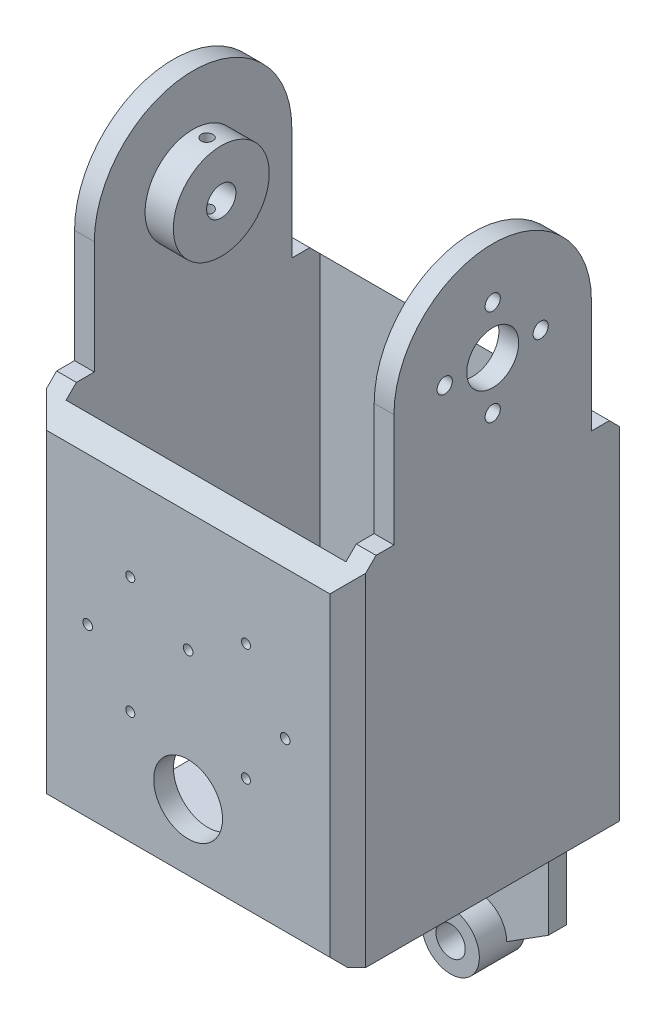
SolidWorks part; units mm, degrees
material "PLA"
ref_plane "Front Plane" through (0, 0, 0) normal (0, 0, 1) x (1, 0, 0)
ref_plane "Top Plane" through (0, 0, 0) normal (0, 1, 0) x (1, 0, 0)
ref_plane "Right Plane" through (0, 0, 0) normal (1, 0, 0) x (0, 0, -1)
sketch "Sketch1" plane through (0, 0, 0) normal (1, 0, 0) x (0, 0, -1)
  line L0 (-17.5, 0) -> (-17.5, -20)
  line L1 (17.5, 0) -> (17.5, -20)
  line L2 (17.5, -20) -> (22.5, -20)
  line L3 (-17.5, -20) -> (-22.5, -20)
  line L4 (22.5, -20) -> (22.5, -76)
  line L5 (-22.5, -20) -> (-22.5, -76)
  line L6 (22.5, -76) -> (-22.5, -76)
  arc A0 (17.5, 0) -> (-17.5, 0) centre (0, 0) ccw
  circle A1 centre (0, 0) radius 4.6
  dimension "D1" = 35
  dimension "D7" = 9.2
  dimension "D2" = 20
  dimension "D3" = 5
  dimension "D4" = 5
  dimension "D5" = 56
  dimension "D6" = 56
extrude "Boss-Extrude1" add sketch "Sketch1" against normal blind 3.5
sketch "Sketch2" plane through (0, 0, 0) normal (1, 0, 0) x (0, 0, -1)
  line L7 (-17.5, 0) -> (-17.5, -20)
  line L8 (-17.5, -20) -> (-22.5, -20)
  line L9 (-22.5, -20) -> (-22.5, -76)
  line L10 (-22.5, -76) -> (22.5, -76)
  line L11 (22.5, -76) -> (22.5, -20)
  line L12 (22.5, -20) -> (17.5, -20)
  line L13 (17.5, -20) -> (17.5, 0)
  line L16 (-22.5, -20) -> (-22.5, -76)
  line L17 (-22.5, -76) -> (22.5, -76)
  line L18 (22.5, -76) -> (22.5, -20)
  line L28 (-22.5, -20) -> (-25.675, -20)
  line L29 (-25.675, -20) -> (-25.675, -79.175)
  line L30 (22.5, -20) -> (25.675, -20)
  line L31 (25.675, -20) -> (25.675, -79.175)
  line L45 (-25.675, -79.175) -> (25.675, -79.175)
  arc A1 (17.5, 0) -> (-17.5, 0) centre (0, 0) ccw
  dimension "D2" = 3.175
  dimension "D3" = 3.175
  dimension "D1" = 0
extrude "Boss-Extrude2" add sketch "Sketch2" along normal blind 49.6 and the other way blind 3.5
chamfer "Chamfer2" distance 5 angle 45 2 edges at (23.05, -20, -25.675) (23.05, -20, 25.675)
sketch "Sketch4" plane through (0, -76, 0) normal (0, 1, 0) x (1, 0, 0)
  line L1 (0, 22.5) -> (49.6, 22.5)
  line L2 (0, 22.5) -> (0, -22.5)
  line L3 (0, -22.5) -> (49.6, -22.5)
  line L4 (49.6, 22.5) -> (49.6, -22.5)
extrude "Cut-Extrude1" cut sketch "Sketch4" against normal up to next
sketch "Sketch5" plane through (49.6, 0, 0) normal (1, 0, 0) x (0, 0, -1)
  line L9 (20.675, -20) -> (17.5, -20)
  line L10 (25.675, -25) -> (20.675, -20)
  line L11 (25.675, -79.175) -> (25.675, -25)
  line L12 (-25.675, -79.175) -> (25.675, -79.175)
  line L13 (-25.675, -25) -> (-25.675, -79.175)
  line L14 (-20.675, -20) -> (-25.675, -25)
  line L15 (-17.5, -20) -> (-20.675, -20)
  line L16 (-17.5, 0) -> (-17.5, -20)
  line L17 (17.5, -20) -> (17.5, 0)
  line L18 (20.675, -20) -> (17.5, -20)
  line L19 (25.675, -25) -> (20.675, -20)
  line L20 (25.675, -79.175) -> (25.675, -25)
  line L21 (-25.675, -79.175) -> (25.675, -79.175)
  line L22 (-25.675, -25) -> (-25.675, -79.175)
  line L23 (-20.675, -20) -> (-25.675, -25)
  line L24 (-17.5, -20) -> (-20.675, -20)
  line L25 (-17.5, 0) -> (-17.5, -20)
  line L26 (17.5, -20) -> (17.5, 0)
  circle A0 centre (0, 0) radius 4.6 construction
  arc A1 (17.5, 0) -> (-17.5, 0) centre (0, 0) ccw
  arc A2 (17.5, 0) -> (-17.5, 0) centre (0, 0) ccw
  circle A3 centre (0, 0) radius 4.6
  dimension "D1" = 0
extrude "Boss-Extrude3" add sketch "Sketch5" along normal blind 3.5
chamfer "Chamfer3" distance 3.175 angle 45 4 edges at (53.1, -52.0875, -25.675) (-3.5, -52.0875, -25.675) (53.1, -52.0875, 25.675) (-3.5, -52.0875, 25.675)
sketch "Sketch6" plane through (0, 0, 0) normal (1, 0, 0) x (0, 0, -1)
  circle A0 centre (0, 0) radius 8.5
  circle A1 centre (0, 0) radius 2.6
  dimension "D1" = 17
  dimension "D2" = 5.2
extrude "Boss-Extrude4" add sketch "Sketch6" along normal blind 5
sketch "Sketch7" plane through (0, -79.175, 0) normal (0, -1, 0) x (1, 0, 0)
  line L0 (2.5, 8.5) -> (2.5, -8.5) construction
  line L1 (5, 8.5) -> (0, 8.5) construction
  line L2 (0, -8.5) -> (5, -8.5) construction
  line L3 (5, 0) -> (0, 0) construction
  line L4 (5, -8.5) -> (5, 8.5) construction
  circle A0 centre (2.5, 0) radius 1.025
  dimension "D1" = 2.05
extrude "Cut-Extrude2" cut sketch "Sketch7" against normal through all
sketch "Sketch9" plane through (53.1, 0, 0) normal (1, 0, 0) x (0, 0, -1)
  circle A0 centre (0, 0) radius 8.5 construction
  circle A1 centre (0, 8.5) radius 1.35
  circle A2 centre (8.5, 0) radius 1.35
  circle A3 centre (0, -8.5) radius 1.35
  circle A4 centre (-8.5, 0) radius 1.35
  dimension "D1" = 17
  dimension "D2" = 2.7
  dimension "D3" = 2.7
  dimension "D4" = 2.7
  dimension "D5" = 2.7
extrude "Cut-Extrude3" cut sketch "Sketch9" against normal up to next
sketch "Sketch10" plane through (0, -79.175, 0) normal (0, -1, 0) x (1, 0, 0)
  line L0 (8.8, 25.675) -> (40.8, 25.675)
  line L1 (-0.325, 25.675) -> (49.925, 25.675) construction
  line L3 (8.8, 25.675) -> (40.8, 25.675)
  line L4 (8.8, 25.675) -> (8.8, -14.325)
  line L5 (8.8, -14.325) -> (40.8, -14.325)
  line L6 (40.8, 25.675) -> (40.8, -14.325)
  line L7 (0, -22.5) -> (0, 22.5) construction
  line L8 (49.6, 22.5) -> (49.6, -22.5) construction
  point P5 (24.8, 25.675)
  line M7 (49.925, 25.675) -> (-0.325, 25.675)
  line M13 (0, 22.5) -> (49.6, 22.5)
  dimension "D1" = 8.8
  dimension "D2" = 40
  dimension "D3" = 8.8
extrude "Boss-Extrude5" add sketch "Sketch10" along normal blind 3.175 contours L6 L4 L5 M13 | L6 L4 M7 M13
chamfer "Chamfer4" distance 1.5785 angle 45 1 edges at (24.8, -82.35, 25.675)
sketch "Sketch11" plane through (0, -79.175, 0) normal (0, -1, 0) x (1, 0, 0)
  line L16 (49.925, 25.675) -> (40.8, 25.675)
  line L17 (40.8, 25.675) -> (40.8, 22.5)
  line L18 (40.8, 22.5) -> (49.6, 22.5)
  line L19 (49.6, 22.5) -> (49.6, -22.5)
  line L20 (49.6, -22.5) -> (0, -22.5)
  line L21 (0, -22.5) -> (0, 22.5)
  line L22 (0, 22.5) -> (8.8, 22.5)
  line L23 (8.8, 22.5) -> (8.8, 25.675)
  line L24 (8.8, 25.675) -> (-0.325, 25.675)
  line L25 (-0.325, 25.675) -> (-3.5, 22.5)
  line L26 (-3.5, 22.5) -> (-3.5, -22.5)
  line L27 (-3.5, -22.5) -> (-0.325, -25.675)
  line L28 (-0.325, -25.675) -> (49.925, -25.675)
  line L29 (49.925, -25.675) -> (53.1, -22.5)
  line L30 (53.1, -22.5) -> (53.1, 22.5)
  line L31 (53.1, 22.5) -> (49.925, 25.675)
  line L32 (49.925, 25.675) -> (40.8, 25.675)
  line L33 (40.8, 25.675) -> (40.8, 22.5)
  line L34 (40.8, 22.5) -> (49.6, 22.5)
  line L35 (49.6, 22.5) -> (49.6, -22.5)
  line L36 (49.6, -22.5) -> (0, -22.5)
  line L37 (0, -22.5) -> (0, 22.5)
  line L38 (0, 22.5) -> (8.8, 22.5)
  line L39 (8.8, 22.5) -> (8.8, 25.675)
  line L40 (8.8, 25.675) -> (-0.325, 25.675)
  line L41 (-0.325, 25.675) -> (-3.5, 22.5)
  line L42 (-3.5, 22.5) -> (-3.5, -22.5)
  line L43 (-3.5, -22.5) -> (-0.325, -25.675)
  line L44 (-0.325, -25.675) -> (49.925, -25.675)
  line L45 (49.925, -25.675) -> (53.1, -22.5)
  line L46 (53.1, -22.5) -> (53.1, 22.5)
  line L47 (53.1, 22.5) -> (49.925, 25.675)
  dimension "D1" = 0
extrude "Boss-Extrude6" add sketch "Sketch11" along normal blind 3.175
chamfer "Chamfer5" distance 1.5785 angle 45 2 edges at (4.2375, -82.35, 25.675) (45.3625, -82.35, 25.675)
sketch "Sketch12" plane through (0, 0, 25.675) normal (0, 0, 1) x (1, 0, 0)
  line L0 (14.55, -39.265) -> (14.55, -40.865) construction
  line L1 (35.05, -39.265) -> (35.05, -40.865) construction
  line L2 (35.05, -59.965) -> (35.05, -61.565) construction
  circle A0 centre (24.8, -69.065) radius 6.1
  circle A1 centre (14.55, -40.065) radius 0.8
  circle A2 centre (35.05, -40.065) radius 0.8
  circle A3 centre (35.05, -60.765) radius 0.8
  circle A4 centre (14.55, -60.765) radius 0.8
  dimension "D1" = 12.2
extrude "Cut-Extrude4" cut sketch "Sketch12" against normal up to next
sketch "Sketch13" plane through (0, 0, 22.5) normal (0, 0, -1) x (-1, 0, 0)
  line L0 (-12.4437, -36.1489) -> (-12.4437, -39.9149) construction
  line L1 (-12.4437, -38.0319) -> (-16.9437, -38.0319)
  line L2 (-12.4437, -38.0319) -> (-12.4437, -63.7774)
  line L3 (-12.4437, -63.7774) -> (-16.9437, -63.7774)
  line L4 (-16.9437, -38.0319) -> (-16.9437, -63.7774)
  line L6 (-37.1796, -63.7774) -> (-32.6796, -63.7774)
  line L7 (-37.1796, -63.7774) -> (-37.1796, -38.0319)
  line L8 (-37.1796, -38.0319) -> (-32.6796, -38.0319)
  line L9 (-32.6796, -63.7774) -> (-32.6796, -38.0319)
  circle A0 centre (-35.05, -40.065) radius 0.8 construction
  circle A1 centre (-35.05, -60.765) radius 0.8 construction
  circle A2 centre (-14.55, -60.765) radius 0.8 construction
  circle A3 centre (-14.55, -40.065) radius 0.8 construction
  circle A4 centre (-35.05, -40.065) radius 0.8
  circle A5 centre (-35.05, -60.765) radius 0.8
  circle A6 centre (-14.55, -60.765) radius 0.8
  circle A7 centre (-14.55, -40.065) radius 0.8
  dimension "D1" = 4.5
  dimension "D2" = 4.5
extrude "Boss-Extrude7" add sketch "Sketch13" along normal blind 2.9
sketch "Sketch14" plane through (0, 0, 22.5) normal (0, 0, -1) x (-1, 0, 0)
  line L0 (-35.05, -60.765) -> (-14.55, -60.765) construction
  line L1 (-32.6796, -63.7774) -> (-32.6796, -38.0319) construction
  line L2 (-32.6796, -60.765) -> (-16.9472, -60.765)
  line L3 (-32.6796, -60.765) -> (-32.6796, -79.175)
  line L4 (-32.6796, -79.175) -> (-16.9472, -79.175)
  line L5 (-16.9472, -60.765) -> (-16.9472, -79.175)
  line L6 (-8.8, -79.175) -> (-40.8, -79.175) construction
  circle A0 centre (-24.8, -69.065) radius 6.1 construction
  circle A1 centre (-24.8, -69.065) radius 6.1
extrude "Boss-Extrude8" add sketch "Sketch14" along normal blind 0.325
sketch "Sketch20" plane through (0, 0, -25.675) normal (0, 0, -1) x (-1, 0, 0)
  line L0 (3.5, -82.35) -> (-53.1, -82.35) construction
  line L1 (-37.3, -79.38) -> (-37.3, -109.38)
  line L2 (-12.3, -79.38) -> (-12.3, -109.38)
  line L3 (-37.3, -109.38) -> (-29.9, -114.0625)
  line L4 (-53.1, -82.35) -> (-53.1, -21.825) construction
  line L9 (-37.3, -69.38) -> (-12.3, -69.38)
  line L10 (-37.3, -69.38) -> (-37.3, -79.38)
  line L12 (-12.3, -69.38) -> (-12.3, -79.38)
  line L14 (-19.7, -114.0625) -> (-12.3, -109.38)
  circle A4 centre (-24.8, -114.0625) radius 2.6
  circle A5 centre (-24.8, -114.0625) radius 5.1
  dimension "D1" = 5.2
  dimension "D4" = 10.2
  dimension "D5" = 15.8
  dimension "D2" = 10
  dimension "D3" = 25
  dimension "D6" = 12.97
  dimension "D7" = 30
  dimension "D8" = 30
extrude "Boss-Extrude11" add sketch "Sketch20" along normal blind 3.175
sketch "Sketch21" plane through (0, 0, -25.675) normal (0, 0, 1) x (1, 0, 0)
  circle A9 centre (24.8, -114.0625) radius 5.1
  circle A10 centre (24.8, -114.0625) radius 2.6
  dimension "D1" = 10.2
  dimension "D2" = 5.2
extrude "Boss-Extrude12" add sketch "Sketch21" along normal blind 4.84
chamfer "Chamfer10" distance 3.175 angle 45 1 edges at (24.8, -69.38, -25.675)
sketch "Sketch23" plane through (0, 0, 25.675) normal (0, 0, 1) x (1, 0, 0)
  circle A0 centre (7.0013, -51.165) radius 0.85
  circle A2 centre (24.8, -46.165) radius 0.85
  circle A4 centre (42.0013, -51.165) radius 0.85
extrude "Cut-Extrude5" cut sketch "Sketch23" against normal up to next
